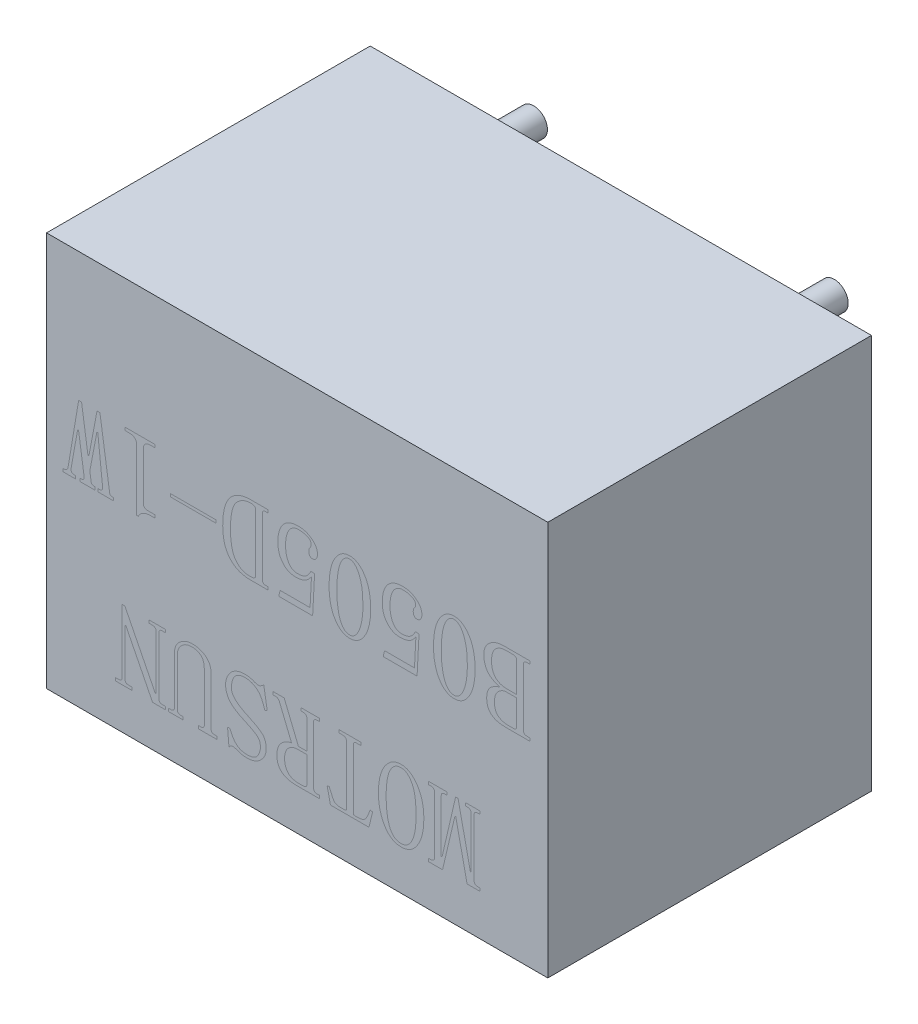
SolidWorks part; units mm, degrees
ref_plane "前视基准面" through (0, 0, 0) normal (0, 0, 1) x (1, 0, 0)
ref_plane "上视基准面" through (0, 0, 0) normal (0, 1, 0) x (1, 0, 0)
ref_plane "右视基准面" through (0, 0, 0) normal (1, 0, 0) x (0, 0, -1)
sketch "草图1" plane through (0, 0, 0) normal (0, 0, 1) x (1, 0, 0)
  line L0 (0, 0) -> (12.7, 0)
  line L1 (12.7, 0) -> (12.7, 10)
  line L2 (12.7, 10) -> (0, 10)
  line L3 (0, 10) -> (0, 0)
  line L4 (0, 0) -> (-0.4773, 0.1591)
  dimension "D1" = 12.7
  dimension "D2" = 10
extrude "凸台-拉伸1" add sketch "草图1" along normal blind 8.2 contours L2 L3 L0 L1 region at (6.35, 5, 0)
sketch "草图2" plane through (0, 0, 0) normal (0, 0, -1) x (-1, 0, 0)
  line L0 (-12.7, 5) -> (0, 5) construction
  line L1 (-12.7, 0) -> (-12.7, 10) construction
  line L2 (0, 10) -> (0, 0) construction
  line L3 (-6.35, 10) -> (-6.35, 0) construction
  line L4 (-12.7, 10) -> (0, 10) construction
  line L5 (0, 0) -> (-12.7, 0) construction
  circle A0 centre (-10.16, 8.81) radius 0.35
  circle A1 centre (-2.54, 8.81) radius 0.35
  circle A2 centre (-2.54, 1.19) radius 0.35
  circle A3 centre (-7.62, 1.19) radius 0.35
  dimension "D1" = 0.7
  dimension "D2" = 7.62
  dimension "D3" = 7.62
  dimension "D4" = 0.7
  dimension "D5" = 5.08
extrude "凸台-拉伸2" add sketch "草图2" along normal blind 1.6
sketch "草图3" plane through (0, 0, 8.2) normal (0, 0, 1) x (1, 0, 0)
  line L0 (12.7, 2.8545) -> (0, 2.8545) construction
  line L1 (12.7, 0) -> (12.7, 10) construction
  line L2 (0, 10) -> (0, 0) construction
  line L3 (12.7, 6.78) -> (0, 6.78) construction
  text T0 "MOTRSUN" height in points 5
  text T1 "B0505D-1W" height in points 5
wrap "包覆1" sketch "草图3" wrap type scribe source sketch "草图3" face at (6.35, 5, 8.2)
